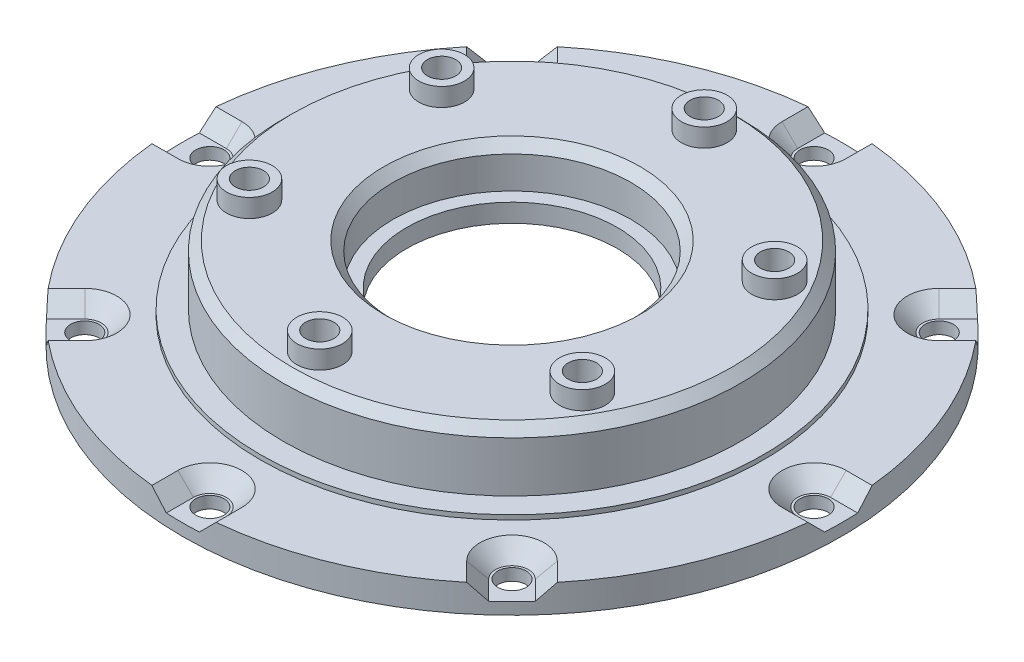
SolidWorks part; units mm, degrees
material "PLA"
ref_plane "Front Plane" through (0, 0, 0) normal (0, 0, 1) x (1, 0, 0)
ref_plane "Top Plane" through (0, 0, 0) normal (0, 1, 0) x (1, 0, 0)
ref_plane "Right Plane" through (0, 0, 0) normal (1, 0, 0) x (0, 0, -1)
sketch "Sketch1" plane through (0, 0, 0) normal (0, 1, 0) x (1, 0, 0)
  circle A0 centre (0, 0) radius 36
  dimension "D1" = 72
extrude "Boss-Extrude1" add sketch "Sketch1" along normal blind 3
sketch "Sketch2" plane through (0, 3, 0) normal (0, 1, 0) x (1, 0, 0)
  circle A0 centre (0, 0) radius 27.5
  dimension "D1" = 55
extrude "Boss-Extrude2" add sketch "Sketch2" along normal blind 0.5
sketch "Sketch3" plane through (0, 3.5, 0) normal (0, 1, 0) x (1, 0, 0)
  circle A0 centre (0, 0) radius 25
  dimension "D1" = 50
extrude "Boss-Extrude3" add sketch "Sketch3" along normal blind 6.5
sketch "Sketch4" plane through (0, 10, 0) normal (0, 1, 0) x (1, 0, 0)
  circle A0 centre (0, 0) radius 13
  dimension "D1" = 26
extrude "Cut-Extrude1" cut sketch "Sketch4" against normal blind 4.5
sketch "Sketch5" plane through (0, 5.5, 0) normal (0, 1, 0) x (1, 0, 0)
  circle A0 centre (0, 0) radius 11.5
  dimension "D1" = 23
extrude "Cut-Extrude2" cut sketch "Sketch5" against normal up to surface (5.5 mm away) up to face at (0, 0, 36)
sketch "Sketch6" plane through (0, 3, 0) normal (0, 1, 0) x (1, 0, 0)
  circle A0 centre (0, 0) radius 33 construction
  circle A1 centre (0, 33) radius 1.55
  dimension "D1" = 66
  dimension "D2" = 3.1
extrude "Cut-Extrude3" cut sketch "Sketch6" against normal up to surface (3 mm away) up to face at (0, 0, 11.5)
sketch "Sketch8" plane through (0, 10, 0) normal (0, 1, 0) x (1, 0, 0)
  line L0 (0, 0) -> (0, 21) construction
  circle A0 centre (0, 21) radius 1.55
  dimension "D2" = 3.1
  dimension "D1" = 21
extrude "Cut-Extrude5" cut sketch "Sketch8" against normal up to surface (10 mm away) up to face at (0, 0, -31.45)
sketch "Sketch9" plane through (0, 0, 0) normal (0, -1, 0) x (1, 0, 0)
  circle A0 centre (0, -21) radius 2.15
  dimension "D1" = 4.3
extrude "Cut-Extrude6" cut sketch "Sketch9" against normal blind 6
chamfer "Chamfer3" distance 1 angle 45 2 edges at (0, 10, 25) (0, 10, 13)
sketch "Sketch11" plane through (0, 3, 0) normal (0, 1, 0) x (1, 0, 0)
  line L2 (-3.5, 33) -> (-3.5, 37.8775)
  line L3 (-3.5, 37.8775) -> (3.5, 37.8775)
  line L4 (3.5, 33) -> (3.5, 37.8775)
  arc A0 (-3.5, 33) -> (3.5, 33) centre (0, 33) ccw
  dimension "D1" = 7
extrude "Cut-Extrude7" cut sketch "Sketch11" against normal blind 1.7
chamfer "Chamfer6" distance 1.7 angle 45 3 edges at (-3.5, 1.3, -34.4147) (3.5, 1.3, -34.4147) (0, 1.3, -29.5)
chamfer "Chamfer7" distance 1 angle 35 1 edges at (0, 0, -23.15) first distance on face at (0, 0, -23.15)
pattern_circular "CirPattern1" count 6 over 360 about axis through (0, 3, 0) along (0, -1, 0) of "Cut-Extrude5", "Cut-Extrude6", "Chamfer7" reverse direction yes
sketch "Sketch14" plane through (0, 0, 0) normal (0, -1, 0) x (1, 0, 0)
  circle A0 centre (0, 0) radius 16.5
  dimension "D1" = 33
extrude "Cut-Extrude9" cut sketch "Sketch14" against normal blind 3.5
chamfer "Chamfer8" distance 0.5 angle 45 2 edges at (0, 3.5, -16.5) (0, 0, -16.5)
sketch "Sketch15" plane through (0, 0, 0) normal (0, -1, 0) x (1, 0, 0)
  line L0 (0, 6.3878) -> (0, 0) construction
  line L1 (0, 0) -> (-4.6793, 8.1048) construction
  line L2 (-15.1376, 18.0403) -> (0, 0) construction
  line L3 (0, 0) -> (-8.0546, 22.1298) construction
  line L4 (-15.1376, 18.0403) -> (-17.6445, 21.0279)
  line L5 (-8.0546, 22.1298) -> (-9.3885, 25.7946)
  arc A0 (-8.0546, 22.1298) -> (-15.1376, 18.0403) centre (0, 0) ccw
  arc A1 (-9.3885, 25.7946) -> (-17.6445, 21.0279) centre (0, 0) ccw
  dimension "D1" = 47.1
  dimension "D2" = 54.9
  dimension "D3" = 30
  dimension "D4" = 10
  dimension "D5" = 10
extrude "Boss-Extrude4" add sketch "Sketch15" along normal blind 3
fillet "Fillet1" radius 1.5 8 edges at (-16.3911, -3, 19.5341) (-13.725, -3, 23.7724) (-8.7215, -3, 23.9622) (-11.775, -3, 20.3949) (-9.3885, -1.5, 25.7946) (-8.0546, -1.5, 22.1298) (-17.6445, -1.5, 21.0279) (-15.1376, -1.5, 18.0403)
pattern_circular "CirPattern2" count 6 over 360 about axis through (0, 3, 0) along (0, -1, 0) of "Fillet1", "Boss-Extrude4" reverse direction yes
pattern_circular "CirPattern3" count 8 over 360 about axis through (0, 3, 0) along (0, -1, 0) of "Chamfer6", "Cut-Extrude3", "Cut-Extrude7" reverse direction yes
sketch "Sketch16" plane through (0, 10, 0) normal (0, 1, 0) x (1, 0, 0)
  circle A0 centre (0, 21) radius 1.55
  circle A1 centre (0, 21) radius 2.5
  dimension "D1" = 3.1
  dimension "D2" = 5
extrude "Boss-Extrude5" add sketch "Sketch16" along normal blind 2
pattern_circular "CirPattern4" count 6 over 360 about axis through (0, 3, 0) along (0, -1, 0) of "Boss-Extrude5"
sketch "Sketch18" plane through (0, 0, 0) normal (0, -1, 0) x (1, 0, 0)
  line L0 (-15.9099, 15.9099) -> (0, 0) construction
  line L1 (0, 0) -> (-5.8234, 21.7333) construction
  line L2 (-4.5225, 7.8333) -> (0, 0) construction
  line L3 (0, 0) -> (0, 8.0116) construction
  line L4 (-15.9099, 15.9099) -> (-13.0815, 13.0815)
  line L5 (-5.8234, 21.7333) -> (-4.7882, 17.8696)
  arc A0 (-5.8234, 21.7333) -> (-15.9099, 15.9099) centre (0, 0) ccw
  arc A1 (-4.7882, 17.8696) -> (-13.0815, 13.0815) centre (0, 0) ccw
  dimension "D1" = 45
  dimension "D2" = 37
  dimension "D3" = 30
  dimension "D4" = 15
  dimension "D5" = 15
extrude "Cut-Extrude10" cut sketch "Sketch18" against normal blind 6.5
fillet "Fillet2" radius 1 4 edges at (-15.9099, 3.25, 15.9099) (-13.0815, 3.25, 13.0815) (-4.7882, 3.25, 17.8696) (-5.8234, 3.25, 21.7333)
chamfer "Chamfer9" distance 0.5 angle 45 8 edges at (-11.25, 0, 19.4856) (-15.479, 0, 15.9167) (-6.0448, 0, 21.3635) (-14.4784, 0, 14.4784) (-5.2995, 0, 19.7778) (-13.089, 0, 13.4779) (-5.1277, 0, 18.0743) (-9.25, 0, 16.0215)
pattern_circular "CirPattern5" count 6 over 360 about axis through (0, 3.5, 0) along (0, -1, 0) of "Cut-Extrude10", "Fillet2", "Chamfer9" reverse direction yes
